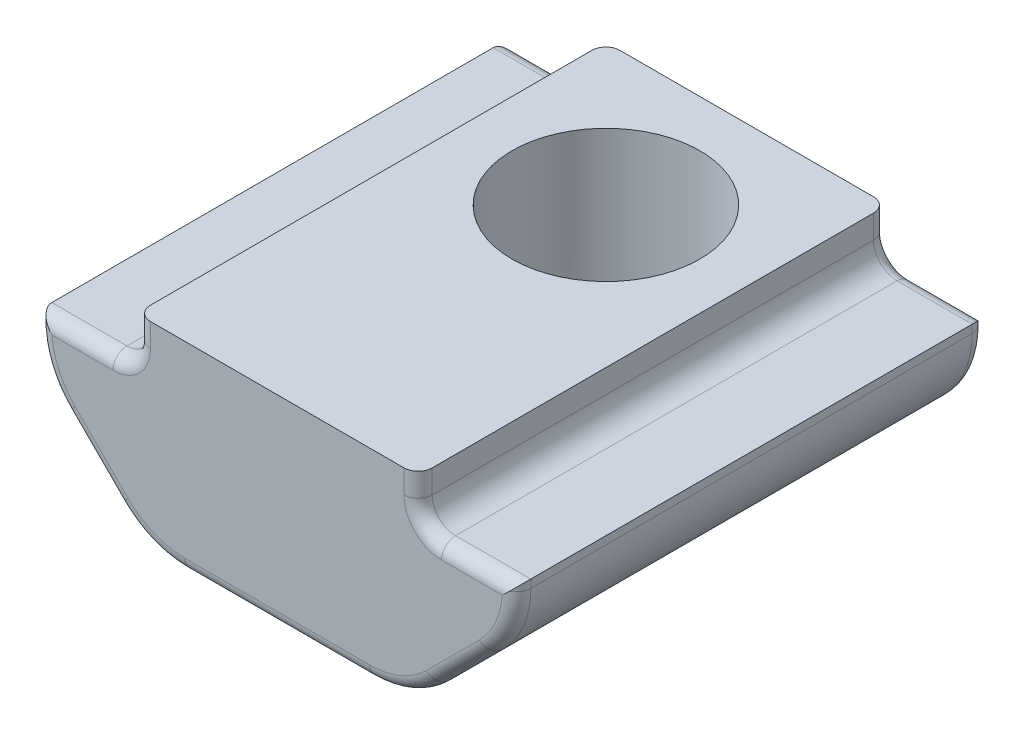
SolidWorks part; units mm, degrees
material "不锈钢 (铁素体)"
ref_plane "前视基准面" through (0, 0, 0) normal (0, 0, 1) x (1, 0, 0)
ref_plane "上视基准面" through (0, 0, 0) normal (0, 1, 0) x (1, 0, 0)
ref_plane "右视基准面" through (0, 0, 0) normal (1, 0, 0) x (0, 0, -1)
sketch "草图1" plane through (0, 0, 0) normal (0, 0, 1) x (1, 0, 0)
  line L0 (0, 0) -> (0, 8533.2886) construction
  line L1 (-3, 4.3) -> (3, 4.3)
  line L2 (3, 4.3) -> (3, 3.8)
  line L3 (3.5, 3.3) -> (5.1, 3.3)
  line L4 (5.1, 3.3) -> (5.1, 3.1284)
  line L5 (4.5142, 1.7142) -> (3.3858, 0.5858)
  line L6 (1.9716, 0) -> (-1.9716, 0)
  line L7 (-4.5142, 1.7142) -> (-3.3858, 0.5858)
  line L8 (-5.1, 3.3) -> (-5.1, 3.1284)
  line L9 (-3.5, 3.3) -> (-5.1, 3.3)
  line L10 (-3, 4.3) -> (-3, 3.8)
  arc A0 (-5.1, 3.1284) -> (-4.5142, 1.7142) centre (-3.1, 3.1284) ccw
  arc A1 (5.1, 3.1284) -> (4.5142, 1.7142) centre (3.1, 3.1284) cw
  arc A2 (1.9716, 0) -> (3.3858, 0.5858) centre (1.9716, 2) ccw
  arc A3 (-3.3858, 0.5858) -> (-1.9716, 0) centre (-1.9716, 2) ccw
  arc A4 (-3.5, 3.3) -> (-3, 3.8) centre (-3.5, 3.8) ccw
  arc A5 (3.5, 3.3) -> (3, 3.8) centre (3.5, 3.8) cw
  point P11 (0, 0)
  point P15 (0, 4.3)
  point P17 (-5.1, 2.3)
  point P20 (5.1, 2.3)
  point P23 (2.8, 0)
  point P26 (-2.8, 0)
  point P29 (-3, 3.3)
  point P32 (3, 3.3)
  dimension "D7" = 2
  dimension "D8" = 0.5
  dimension "D1" = 3.3
  dimension "D2" = 10.2
  dimension "D3" = 4.3
  dimension "D4" = 45
  dimension "D5" = 1
  dimension "D6" = 6
extrude "凸台-拉伸1" add sketch "草图1" along normal blind 10
fillet "圆角3" radius 0.3 30 edges at (-5.1, 3.2142, 10) (-3, 4.05, 10) (3, 4.05, 0) (5.1, 3.2142, 0) (3.95, 1.15, 10) (2.7369, 0.1522, 10) (0, 0, 10) (-2.7369, 0.1522, 10) (-3.95, 1.15, 10) (-4.9478, 2.3631, 10) (-4.3, 3.3, 10) (-3.1464, 3.4464, 10) (4.3, 3.3, 0) (3.1464, 3.4464, 0) (-3.95, 1.15, 0) (-2.7369, 0.1522, 0) (0, 0, 0) (2.7369, 0.1522, 0) (3.95, 1.15, 0) (4.9478, 2.3631, 0) (5.1, 3.2142, 10) (4.9478, 2.3631, 10) (-5.1, 3.2142, 0) (-4.9478, 2.3631, 0) (3, 4.05, 10) (3.1464, 3.4464, 10) (-3, 4.05, 0) (-3.1464, 3.4464, 0) (4.3, 3.3, 10) (-4.3, 3.3, 0)
sketch "草图2" plane through (0, 4.3, 0) normal (0, 1, 0) x (1, 0, 0)
  circle A0 centre (0, -3) radius 2
  dimension "D1" = 4
  dimension "D2" = 3
extrude "切除-拉伸1" cut sketch "草图2" against normal blind 6
